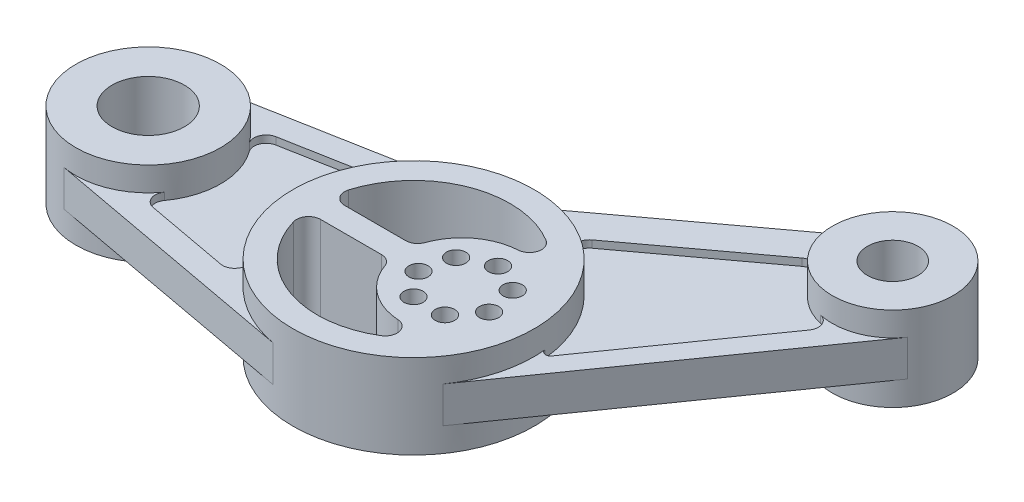
SolidWorks part; units mm, degrees
ref_plane "Front Plane" through (0, 0, 0) normal (0, 0, 1) x (1, 0, 0)
ref_plane "Top Plane" through (0, 0, 0) normal (0, 1, 0) x (1, 0, 0)
ref_plane "Right Plane" through (0, 0, 0) normal (1, 0, 0) x (0, 0, -1)
sketch "Sketch1" plane through (0, 0, 0) normal (0, 1, 0) x (1, 0, 0)
  line L0 (0, 0) -> (0, 36220.0453) construction
  line L1 (0, 0) -> (-36220.0453, 0) construction
  line L2 (-130, 0) -> (-130, 36220.0453) construction
  line L3 (0, 0) -> (22794.013, 28148.2619) construction
  line L4 (-20, 0) -> (-20, 50000) construction
  line L5 (-53.541, 5) -> (-28.2843, 5)
  line L6 (-53.541, -5) -> (-28.2843, -5)
  line L7 (-135.4545, 29.5) -> (-29.0909, 49.1666)
  line L8 (-135.4545, -29.5) -> (-29.0909, -49.1666)
  line L9 (65.058, 118.7976) -> (-29.0909, 49.1666)
  line L10 (100.3773, 84.3223) -> (20.9073, -28.7505)
  line L11 (-102.5407, -25.4162) -> (-68.2388, -31.7587)
  line L12 (-102.5407, 25.4162) -> (-68.2388, 31.7587)
  line L13 (0, 53.8658) -> (50.0737, 90.8995)
  line L14 (77.4313, 66.5537) -> (33.2807, 3.7345)
  circle A0 centre (-130, 0) radius 30
  circle A1 centre (-130, 0) radius 15
  circle A2 centre (0, 0) radius 15 construction
  circle A3 centre (0, 0) radius 22
  arc A4 (-23.5702, -8.3333) -> (-1.5625, -24.9511) centre (0, 0) ccw
  circle A5 centre (0, 15) radius 4
  circle A6 centre (11.7275, 9.3523) radius 4
  circle A7 centre (14.6239, -3.3378) radius 4
  circle A8 centre (6.5083, -13.5145) radius 4
  circle A9 centre (-6.5083, -13.5145) radius 4
  circle A10 centre (-14.6239, -3.3378) radius 4
  circle A11 centre (-11.7275, 9.3523) radius 4
  circle A12 centre (79.9237, 98.6975) radius 10.5
  circle A13 centre (79.9237, 98.6975) radius 25
  circle A14 centre (-20, 0) radius 50
  arc A15 (-58.3326, -11.4286) -> (0.7143, -34.2187) centre (-20, 0) ccw
  arc A16 (-1.5625, 24.9511) -> (-23.5702, 8.3333) centre (0, 0) ccw
  circle A17 centre (0, 0) radius 25 construction
  arc A18 (-58.3326, 11.4286) -> (-53.541, 5) centre (-53.541, 10) ccw
  arc A19 (0.7143, 34.2187) -> (-58.3326, 11.4286) centre (-20, 0) ccw
  arc A20 (-23.5702, 8.3333) -> (-28.2843, 5) centre (-28.2843, 10) cw
  arc A21 (0.7143, 34.2187) -> (-1.5625, 24.9511) centre (-1.875, 29.9413) cw
  arc A22 (0.7143, -34.2187) -> (-1.5625, -24.9511) centre (-1.875, -29.9413) ccw
  arc A23 (-23.5702, -8.3333) -> (-28.2843, -5) centre (-28.2843, -10) ccw
  arc A24 (-58.3326, -11.4286) -> (-53.541, -5) centre (-53.541, -10) cw
  arc A25 (-105.6842, -17.5711) -> (-102.5407, -25.4162) centre (-101.6316, -20.4996) ccw
  arc A26 (-68.2388, -31.7587) -> (-62.3355, -26.6028) centre (-67.3297, -26.842) ccw
  arc A27 (-108.2816, -31.6187) -> (-102.5407, -25.4162) centre (-103.4498, -30.3329) cw
  arc A28 (-68.2388, 31.7587) -> (-62.3355, 26.6028) centre (-67.3297, 26.842) cw
  arc A29 (-105.6842, 17.5711) -> (-102.5407, 25.4162) centre (-101.6316, 20.4996) cw
  arc A30 (0, 53.8658) -> (0, 45.8258) centre (2.9731, 49.8458) ccw
  arc A31 (50.0737, 90.8995) -> (56.2238, 90.7404) centre (53.0469, 86.8795) cw
  arc A32 (33.2807, 3.7345) -> (29.7682, 4.8088) centre (31.7472, 5) cw
  arc A33 (74.4378, 74.3069) -> (77.4313, 66.5537) centre (73.3406, 69.4287) cw
  point P32 (0, 0)
  point P41 (-59.6863, 5)
  point P49 (-24.4949, 5)
  point P52 (14.375, 20.4538)
  point P57 (-24.4949, -5)
  point P60 (-59.6863, -5)
  dimension "D3" = 30
  dimension "D4" = 60
  dimension "D5" = 30
  dimension "D6" = 44
  dimension "D7" = 50
  dimension "D8" = 8
  dimension "D10" = 21
  dimension "D11" = 50
  dimension "D13" = 80
  dimension "D14" = 10
  dimension " 100" = 100
  dimension "D15" = 5
  dimension "D16" = 5
  dimension "D17" = 5
  dimension "D19" = 5
  dimension "D20" = 5
  dimension " 5" = 5
  dimension "D21" = 5
  dimension "D22" = 5
  dimension "D23" = 5
  dimension "D1" = 130
  dimension "D2" = 51
  dimension "D12" = 127
  dimension " " = 20
  dimension "D18" = 10
  dimension "D9" = 7
extrude "Boss-Extrude1" add sketch "Sketch1" along normal blind 35 contours A3 A11 A10 A9 A8 A7 A6 A5 region at (0, 0, 0)
extrude "Boss-Extrude2" add sketch "Sketch1<3>" along normal blind 15 from offset 10 separate body contours A13 A33 L14 A32 A14 L10 | L13 A31 A13 L9 A14 A30 | A0 A29 L12 A28 A14 L7 | A26 L11 A25 A0 L8 A14 region at (-83.5798, 0, -34.0883) region at (19.2122, 0, -76.7805) region at (-83.5798, 0, 34.0883) region at (59.1392, 0, -32.9077)
sketch "Sketch1<3>" plane through (0, 0, 0) normal (0, 1, 0) x (1, 0, 0) same geometry as "Sketch1"
extrude "Boss-Extrude3" add sketch "Sketch1<4>" along normal blind 35 contours A0 A1 | A13 A12 region at (-119.1571, 0, -27.0599) region at (90.8605, 0, -120.3892)
sketch "Sketch1<4>" plane through (0, 0, 0) normal (0, 1, 0) x (1, 0, 0) same geometry as "Sketch1"
extrude "Boss-Extrude5" add sketch "Sketch1<6>" along normal blind 11 from offset 11 contours A29 A0 A25 L11 A26 A14 A28 L12 | A33 A13 A31 L13 A30 A14 A32 L14 region at (-84.2178, 0, 0) region at (39.4694, 0, -52.443)
sketch "Sketch1<6>" plane through (0, 0, 0) normal (0, 1, 0) x (1, 0, 0) same geometry as "Sketch1"
extrude "Boss-Extrude6" add sketch "Sketch1<7>" along normal blind 35 contours A14 A3 A19 A21 A16 A20 L5 A18 A15 A24 L6 A23 A4 A22 region at (-14.4568, 0, -48.2685)
sketch "Sketch1<7>" plane through (0, 0, 0) normal (0, 1, 0) x (1, 0, 0) same geometry as "Sketch1"
